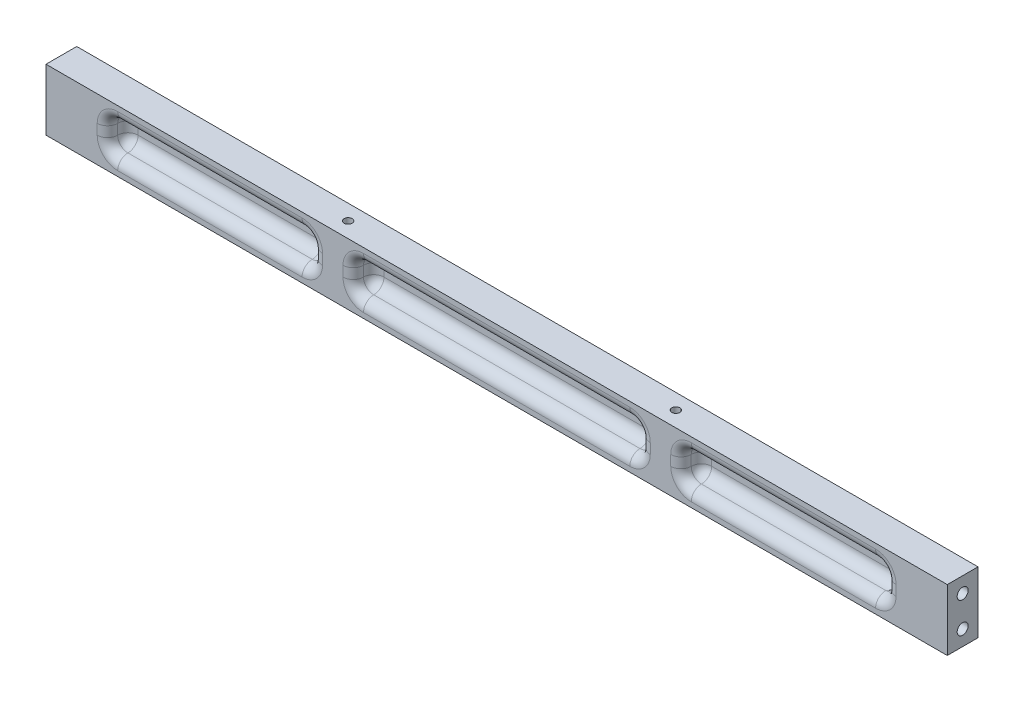
SolidWorks part; units mm, degrees
material "Alum 6061 (Default)"
ref_plane "Front Plane" through (0, 0, 0) normal (0, 0, 1) x (1, 0, 0)
ref_plane "Top Plane" through (0, 0, 0) normal (0, 1, 0) x (1, 0, 0)
ref_plane "Right Plane" through (0, 0, 0) normal (1, 0, 0) x (0, 0, -1)
sketch "Sketch1" plane through (0, 0, 0) normal (0, 0, 1) x (1, 0, 0)
  line L1 (-279.4, 19.05) -> (279.4, 19.05)
  line L2 (-279.4, 19.05) -> (-279.4, -19.05)
  line L3 (-279.4, -19.05) -> (279.4, -19.05)
  line L4 (279.4, 19.05) -> (279.4, -19.05)
  line L5 (-279.4, 19.05) -> (279.4, -19.05) construction
  line L6 (-279.4, -19.05) -> (279.4, 19.05) construction
  point P0 (0, 0)
  dimension "SpreadWidthT" = 558.8
  dimension "Height" = 38.1
extrude "Extrude1" add sketch "Sketch1" along normal mid plane 19.05
hole_wizard "M8x1.25 Tapped Hole1" positions "Sketch6" profile "Sketch7" tap size "M8x1.25" standard "ANSI Metric"
sketch "Sketch6" plane through (-279.4, 0, 0) normal (-1, 0, 0) x (0, 0, 1)
  line L0 (0, 9.525) -> (0, -9.525) construction
  point P0 (0, 9.525)
  point P2 (0, -9.525)
  point P10 (0, 0)
  dimension "D1" = 19.05
sketch "Sketch7" plane through (-279.4, 9.525, 0) normal (0, 1, 0) x (0, 0, 1)
  line L0 (0, 0) -> (0, 21.8549)
  line L1 (0, 21.8549) -> (3.4, 19.812)
  line L2 (3.4, 19.812) -> (3.4, 0)
  line L5 (3.4, 0) -> (0, 0)
  line L10 (0, 21.8549) -> (-3.4, 19.812) construction
  line L11 (0, -6.35) -> (0, 107.95) construction
  dimension "Tap Drill Dia." = 6.8
  dimension "Tap Drill Depth" = 19.812
  dimension "Drill Angle" = 118
cosmetic thread "Hole Thread1" parameters "D1"=16.002, "D2"=8
cosmetic thread "Hole Thread2" parameters "D1"=16.002, "D2"=8
hole_wizard "M8x1.25 Tapped Hole2" positions "Sketch8" profile "Sketch9" tap size "M8x1.25" standard "ANSI Metric"
sketch "Sketch8" plane through (279.4, 0, 0) normal (1, 0, 0) x (0, 0, -1)
  point P0 (0, 9.525)
  point P3 (0, -9.525)
sketch "Sketch9" plane through (279.4, 9.525, 0) normal (0, 1, 0) x (0, 0, -1)
  line L0 (0, 0) -> (0, 21.8549)
  line L1 (0, 21.8549) -> (3.4, 19.812)
  line L2 (3.4, 19.812) -> (3.4, 0)
  line L5 (3.4, 0) -> (0, 0)
  line L10 (0, 21.8549) -> (-3.4, 19.812) construction
  line L11 (0, -6.35) -> (0, 107.95) construction
  dimension "Tap Drill Dia." = 6.8
  dimension "Tap Drill Depth" = 19.812
  dimension "Drill Angle" = 118
cosmetic thread "Hole Thread3" parameters "D1"=16.002, "D2"=8
cosmetic thread "Hole Thread4" parameters "D1"=16.002, "D2"=8
hole_wizard "M6x1.0 Tapped Hole1" positions "Sketch10" profile "Sketch11" tap size "M6x1.0" standard "ANSI Metric"
sketch "Sketch10" plane through (0, 19.05, 0) normal (0, 1, 0) x (1, 0, 0)
  line L0 (-101.6, 0) -> (101.6, 0) construction
  line L1 (-279.4, -9.525) -> (-279.4, 9.525) construction
  point P15 (-101.6, 0)
  point P17 (101.6, 0)
  point P24 (0, 0)
  dimension "D2" = 177.8
sketch "Sketch11" plane through (-101.6, 19.05, 0) normal (1, 0, 0) x (0, 0, 1)
  line L0 (0, 0) -> (0, 14.2022)
  line L1 (0, 14.2022) -> (2.5, 12.7)
  line L2 (2.5, 12.7) -> (2.5, 0)
  line L5 (2.5, 0) -> (0, 0)
  line L10 (0, 14.2022) -> (-2.5, 12.7) construction
  line L11 (0, -6.35) -> (0, 107.95) construction
  dimension "Tap Drill Dia." = 5
  dimension "Tap Drill Depth" = 12.7
  dimension "Drill Angle" = 118
cosmetic thread "Hole Thread5" parameters "D1"=12.7, "D2"=6
cosmetic thread "Hole Thread6" parameters "D1"=12.7, "D2"=6
sketch "Sketch12" plane through (0, 0, 9.525) normal (0, 0, 1) x (1, 0, 0)
  line L0 (-279.4, 19.05) -> (-279.4, -19.05) construction
  line L13 (-88.9, 9.525) -> (88.9, 9.525)
  line L14 (-88.9, 9.525) -> (-88.9, -9.525)
  line L15 (-88.9, -9.525) -> (88.9, -9.525)
  line L16 (88.9, 9.525) -> (88.9, -9.525)
  line L17 (-88.9, 9.525) -> (88.9, -9.525) construction
  line L18 (-88.9, -9.525) -> (88.9, 9.525) construction
  line L19 (114.3, 9.525) -> (241.3, 9.525)
  line L20 (114.3, 9.525) -> (114.3, -9.525)
  line L21 (114.3, -9.525) -> (241.3, -9.525)
  line L22 (241.3, 9.525) -> (241.3, -9.525)
  line L23 (114.3, 9.525) -> (241.3, -9.525) construction
  line L24 (114.3, -9.525) -> (241.3, 9.525) construction
  line L25 (-241.3, 9.525) -> (-114.3, 9.525)
  line L26 (-241.3, 9.525) -> (-241.3, -9.525)
  line L27 (-241.3, -9.525) -> (-114.3, -9.525)
  line L28 (-114.3, 9.525) -> (-114.3, -9.525)
  line L29 (-241.3, 9.525) -> (-114.3, -9.525) construction
  line L30 (-241.3, -9.525) -> (-114.3, 9.525) construction
  point P0 (0, 0)
  point P5 (177.8, 0)
  point P10 (-177.8, 0)
  dimension "D1" = 19.05
  dimension "D2" = 25.4
  dimension "D3" = 38.1
  dimension "D5" = 25.4
  dimension "D6" = 165.1
extrude "Cut-Extrude1" cut sketch "Sketch12" against normal blind 12.7
fillet "Fillet1" radius 6.35 25 edges at (241.3, 0, 9.525) (-114.3, 0, 9.525) (-241.3, 0, 9.525) (241.3, 9.525, 3.175) (177.8, 9.525, -3.175) (177.8, 9.525, 9.525) (114.3, 0, -3.175) (114.3, 0, 9.525) (177.8, -9.525, -3.175) (241.3, -9.525, 3.175) (177.8, -9.525, 9.525) (0, -9.525, -3.175) (0, -9.525, 9.525) (0, 9.525, -3.175) (0, 9.525, 9.525) (88.9, 0, -3.175) (88.9, 0, 9.525) (-88.9, 0, -3.175) (-88.9, 0, 9.525) (-177.8, -9.525, 9.525) (-177.8, 9.525, 9.525) (-177.8, -9.525, -3.175) (-241.3, 0, -3.175) (-177.8, 9.525, -3.175) (-114.3, 0, -3.175)
